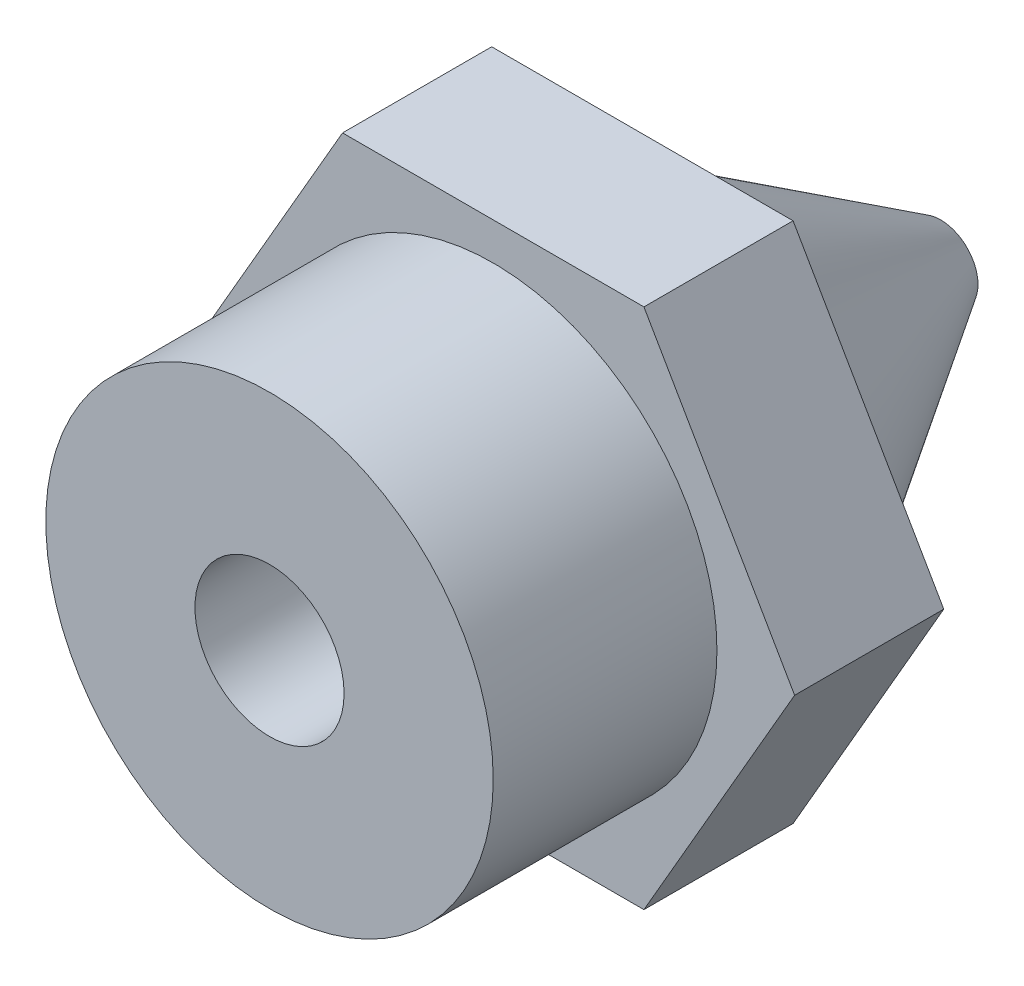
SolidWorks part; units mm, degrees
ref_plane "Plan de face" through (0, 0, 0) normal (0, 0, 1) x (1, 0, 0)
ref_plane "Plan de dessus" through (0, 0, 0) normal (0, 1, 0) x (1, 0, 0)
ref_plane "Plan de droite" through (0, 0, 0) normal (1, 0, 0) x (0, 0, -1)
sketch "Esquisse1" plane through (0, 0, 0) normal (0, 0, 1) x (1, 0, 0)
  line L1 (4.0415, 0) -> (2.0207, 3.5)
  line L2 (2.0207, 3.5) -> (-2.0207, 3.5)
  line L3 (-2.0207, 3.5) -> (-4.0415, 0)
  line L4 (-4.0415, 0) -> (-2.0207, -3.5)
  line L5 (-2.0207, -3.5) -> (2.0207, -3.5)
  line L6 (2.0207, -3.5) -> (4.0415, 0)
  circle A0 centre (0, 0) radius 3.5 construction
  dimension "D1" = 7
extrude "Boss.-Extru.1" add sketch "Esquisse1" along normal blind 9 contours L3 L4 L5 L6 L1 L2
sketch "Esquisse2" plane through (0, 0, 9) normal (0, 0, 1) x (1, 0, 0)
  line L1 (-9.4849, 6.2226) -> (10.1391, 6.2226)
  line L2 (-9.4849, 6.2226) -> (-9.4849, -9.3115)
  line L3 (-9.4849, -9.3115) -> (10.1391, -9.3115)
  line L4 (10.1391, 6.2226) -> (10.1391, -9.3115)
  circle A0 centre (0, 0) radius 3
  dimension "D1" = 6
extrude "Enlèv. mat.-Extru.1" cut sketch "Esquisse2" against normal blind 3
cosmetic thread "Représentation de filetage1" parameters "D1"=3, "D2"=4.891
sketch "Esquisse3" plane through (0, 0, 0) normal (0, 0, -1) x (-1, 0, 0)
  line L1 (5.6434, -6.9413) -> (-5.6238, -6.9413)
  line L2 (5.6434, -6.9413) -> (5.6434, 7.0198)
  line L3 (5.6434, 7.0198) -> (-5.6238, 7.0198)
  line L4 (-5.6238, -6.9413) -> (-5.6238, 7.0198)
  circle A0 centre (0, 0) radius 3
  dimension "D1" = 6
extrude "Enlèv. mat.-Extru.2" cut sketch "Esquisse3" against normal blind 4
chamfer "Chanfrein1" distance 4 angle 32 1 edges at (-3, 0, 0) first distance on face at (-3, 0, 4)
sketch "Esquisse4" plane through (0, 0, 0) normal (0, 1, 0) x (1, 0, 0)
  line L0 (0, -10.3816) -> (0, 2.1166) construction
  line L1 (0, -9) -> (1, -9)
  line L2 (-3, -9) -> (3, -9) construction
  line L3 (0, -9) -> (0, 1.65)
  line L4 (1, -9) -> (1, -6.6)
  line L5 (0, 1.65) -> (1, -6.6)
  line L6 (0, 0) -> (0, -1.4) construction
  line L7 (0, -1.4) -> (0.2, -1.4) construction
  line L8 (0.2, -1.4) -> (0.2, 0) construction
  dimension "D1" = 1
  dimension "D2" = 10.65
  dimension "D3" = 2.4
revolve "Enlèvement de matière-Révolution1" cut sketch "Esquisse4" angle 360 about L0
chamfer "Chanfrein2" [suppressed] distance 0.25 angle 45
